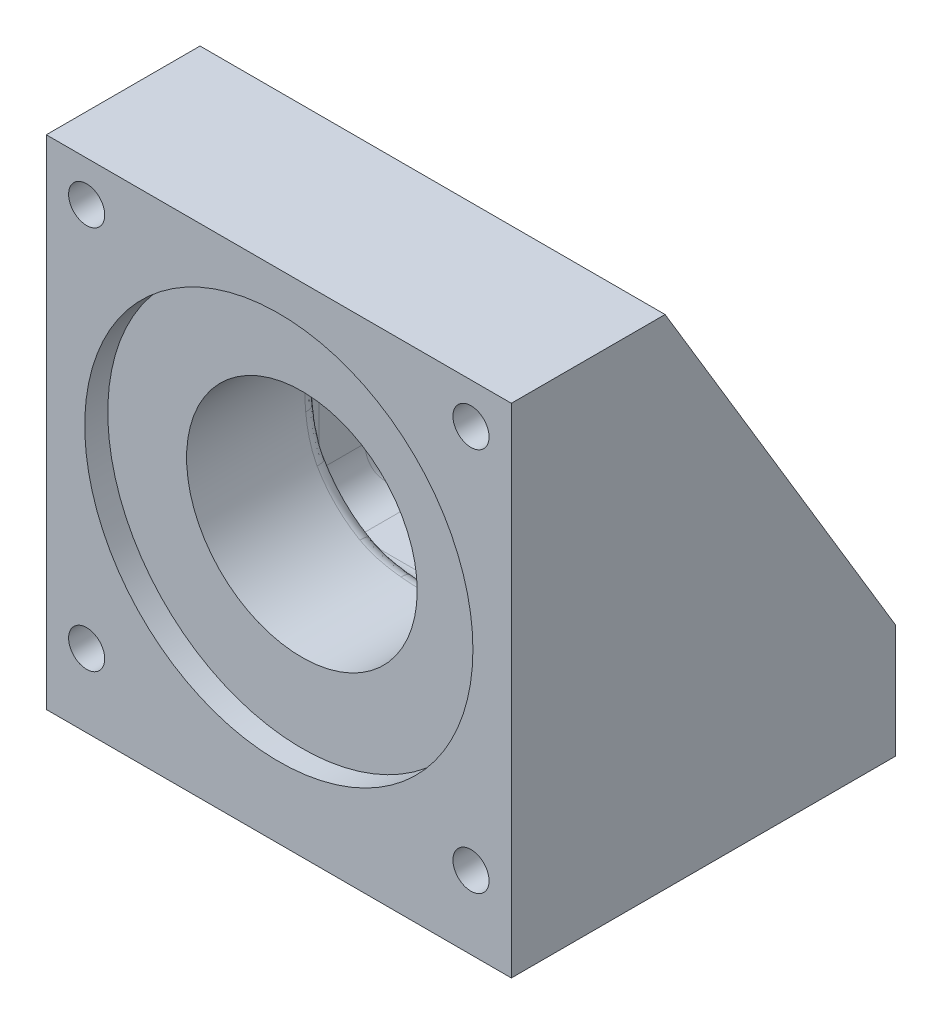
SolidWorks part; units mm, degrees
ref_plane "Front Plane" through (0, 0, 0) normal (0, 0, 1) x (1, 0, 0)
ref_plane "Top Plane" through (0, 0, 0) normal (0, 1, 0) x (1, 0, 0)
ref_plane "Right Plane" through (0, 0, 0) normal (1, 0, 0) x (0, 0, -1)
sketch "Sketch1" plane through (0, 0, 0) normal (0, 0, 1) x (1, 0, 0)
  line L1 (30.25, 30.25) -> (-30.25, 30.25)
  line L2 (30.25, 30.25) -> (30.25, -30.25)
  line L3 (30.25, -30.25) -> (-30.25, -30.25)
  line L4 (-30.25, 30.25) -> (-30.25, -30.25)
  line L5 (30.25, 30.25) -> (-30.25, -30.25) construction
  line L6 (30.25, -30.25) -> (-30.25, 30.25) construction
  line L7 (25, -25) -> (-25, -25) construction
  line L8 (25, -25) -> (25, 25) construction
  line L9 (25, 25) -> (-25, 25) construction
  line L10 (-25, -25) -> (-25, 25) construction
  line L11 (25, -25) -> (-25, 25) construction
  line L12 (25, 25) -> (-25, -25) construction
  circle A0 centre (0, 0) radius 15
  circle A1 centre (-25, 25) radius 2.35
  circle A2 centre (25, 25) radius 2.35
  circle A3 centre (25, -25) radius 2.35
  circle A4 centre (-25, -25) radius 2.35
  point P0 (0, 0)
  dimension "D1" = 30
  dimension "D4" = 4.7
  dimension "D2" = 60.5
  dimension "D3" = 50
extrude "Boss-Extrude1" add sketch "Sketch1" against normal blind 20
sketch "Sketch2" plane through (0, 0, 0) normal (0, 0, 1) x (1, 0, 0)
  circle A0 centre (0, 0) radius 25.25
  dimension "D1" = 50.5
extrude "Cut-Extrude1" cut sketch "Sketch2" against normal blind 3
sketch "Sketch3" plane through (0, 0, -20) normal (0, 0, -1) x (-1, 0, 0)
  line L0 (-19.75, 30.25) -> (-19.75, -19.75)
  line L1 (-19.75, -19.75) -> (19.75, -19.75)
  line L2 (19.75, -19.75) -> (19.75, 30.25)
  line L3 (-19.75, 30.25) -> (-30.25, 30.25)
  line L4 (30.25, -30.25) -> (30.25, 30.25)
  line L5 (30.25, 30.25) -> (-30.25, 30.25)
  line L6 (-30.25, 30.25) -> (-30.25, -30.25)
  line L7 (-30.25, -30.25) -> (30.25, -30.25)
  line L8 (30.25, -30.25) -> (30.25, 30.25)
  line L9 (30.25, 30.25) -> (19.75, 30.25)
  line L10 (-30.25, 30.25) -> (-30.25, -30.25)
  line L11 (-30.25, -30.25) -> (30.25, -30.25)
  line L12 (-19.75, -19.75) -> (-19.75, -30.25) construction
  line L13 (25, 30.25) -> (25, 25) construction
  dimension "D1" = 0
extrude "Boss-Extrude2" add sketch "Sketch3" along normal blind 30
sketch "Sketch4" plane through (-30.25, 0, 0) normal (-1, 0, 0) x (0, 0, 1)
  line L0 (-20, 30.25) -> (-50, -19.75)
  line L1 (-50, -19.75) -> (-50, 30.25)
  line L2 (-50, 30.25) -> (-20, 30.25)
extrude "Cut-Extrude2" cut sketch "Sketch4" against normal through all both and the other way through all
sketch "Sketch7" plane through (0, -30.25, 0) normal (0, -1, 0) x (1, 0, 0)
  line L4 (30.25, 0) -> (-30.25, 0)
  line L5 (-30.25, 0) -> (-30.25, -50)
  line L6 (-30.25, -50) -> (30.25, -50)
  line L7 (30.25, -50) -> (30.25, 0)
  line L8 (30.25, 0) -> (-30.25, 0)
  line L9 (-30.25, 0) -> (-30.25, -50)
  line L10 (-30.25, -50) -> (30.25, -50)
  line L11 (30.25, -50) -> (30.25, 0)
  dimension "D1" = 0
extrude "Boss-Extrude3" add sketch "Sketch7" along normal blind 4.25
fillet "Fillet1" radius 5 5 edges at (19.75, -19.75, -35) (-19.75, -19.75, -35) (-19.75, 5.25, -20) (19.75, 5.25, -20) (0, -19.75, -20)
sketch "Sketch8" plane through (0, 30.25, 0) normal (0, 1, 0) x (1, 0, 0)
  circle A0 centre (-23, 38.25) radius 3.05 construction
  circle A1 centre (-23, 13.25) radius 3.05 construction
  circle A2 centre (23, 13.25) radius 3.05 construction
  circle A3 centre (23, 38.25) radius 3.05 construction
  circle A4 centre (-23, 38.25) radius 3.05
  circle A5 centre (-23, 13.25) radius 3.05 construction
  circle A6 centre (23, 13.25) radius 3.05 construction
  circle A7 centre (23, 38.25) radius 3.05
extrude "Cut-Extrude3" cut sketch "Sketch8" against normal through all both
sketch "Sketch10" plane through (0, 30.25, 0) normal (0, 1, 0) x (1, 0, 0)
  circle A0 centre (-23, 38.25) radius 5.4
  circle A1 centre (23, 38.25) radius 5.4
  circle A2 centre (23, 13.25) radius 5.4 construction
  circle A3 centre (-23, 13.25) radius 5.4 construction
  dimension "D1" = 10.8
extrude "Cut-Extrude4" cut sketch "Sketch10" against normal offset from surface (55 mm away) 5 up to face at (0.0587, -19.75, -33.3323) offset beyond the face yes
fillet "Fillet2" radius 2 6 edges at (19.75, -3.8646, -33.9375) (19.75, -11.0521, -42.5625) (-19.75, -11.0521, -42.5625) (-19.75, -3.8646, -33.9375) (17.6641, -18.813, -37.4202) (-17.6641, -18.813, -39.0798)
sketch "Sketch11" plane through (0, 0, 0) normal (0, 0, 1) x (1, 0, 0)
  circle A0 centre (25, -25) radius 2.35 construction
  circle A1 centre (-25, -25) radius 2.35 construction
  circle A2 centre (-25, 25) radius 2.35 construction
  circle A3 centre (25, 25) radius 2.35 construction
  circle A4 centre (25, -25) radius 2.35
  circle A5 centre (-25, -25) radius 2.35
  circle A6 centre (-25, 25) radius 2.35
  circle A7 centre (25, 25) radius 2.35
extrude "Cut-Extrude5" cut sketch "Sketch11" against normal blind 25
fillet "Fillet3" radius 2 6 edges at (15, 0, -20) (10.6066, -10.6066, -20) (0, -15, -20) (-10.6066, -10.6066, -20) (-15, 0, -20) (0, 15, -20)
